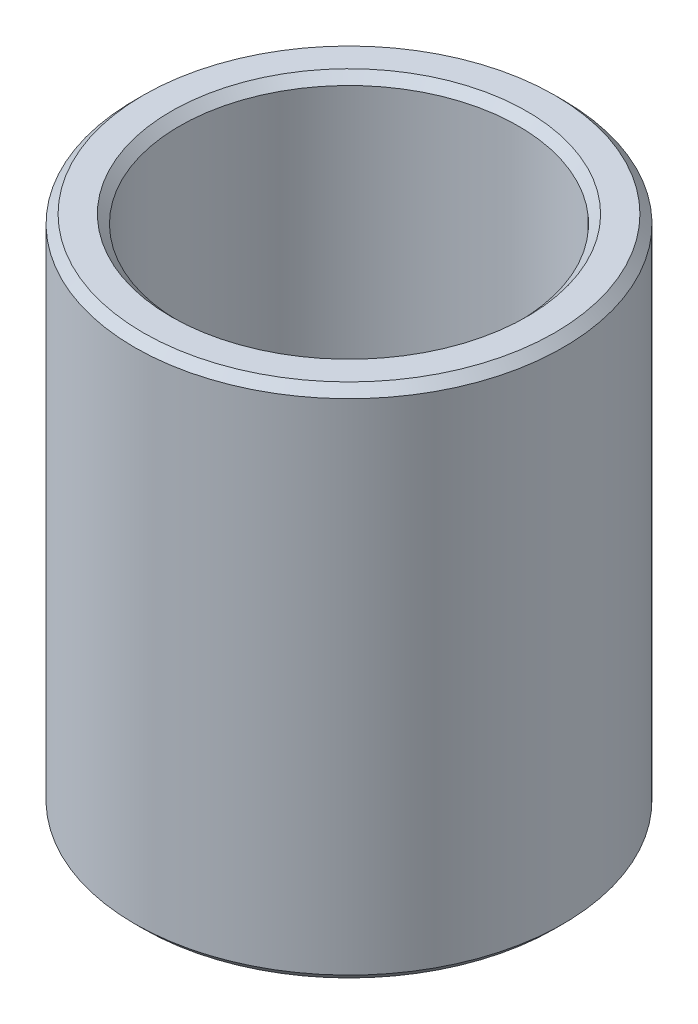
SolidWorks part; units mm, degrees
ref_plane "Front Plane" through (0, 0, 0) normal (0, 0, 1) x (1, 0, 0)
ref_plane "Top Plane" through (0, 0, 0) normal (0, 1, 0) x (1, 0, 0)
ref_plane "Right Plane" through (0, 0, 0) normal (1, 0, 0) x (0, 0, -1)
sketch "Sketch1" plane through (0, 0, 0) normal (0, 1, 0) x (1, 0, 0)
  circle A0 centre (0, 0) radius 35
  dimension "SLEEVE_OD" = 70
extrude "Boss-Extrude1" add sketch "Sketch1" along normal blind 84.326
sketch "Sketch2" plane through (0, 0, 0) normal (0, 1, 0) x (1, 0, 0)
  circle A0 centre (0, 0) radius 27.6759
  dimension "BORE_D" = 55.3518
extrude "Cut-Extrude1" cut sketch "Sketch2" along normal through all
chamfer "Chamfer1" distance 1.3901 angle 45 4 edges at (0, 84.326, 27.6759) (0, 0, 27.6759) (0, 0, 35) (0, 84.326, 35)
